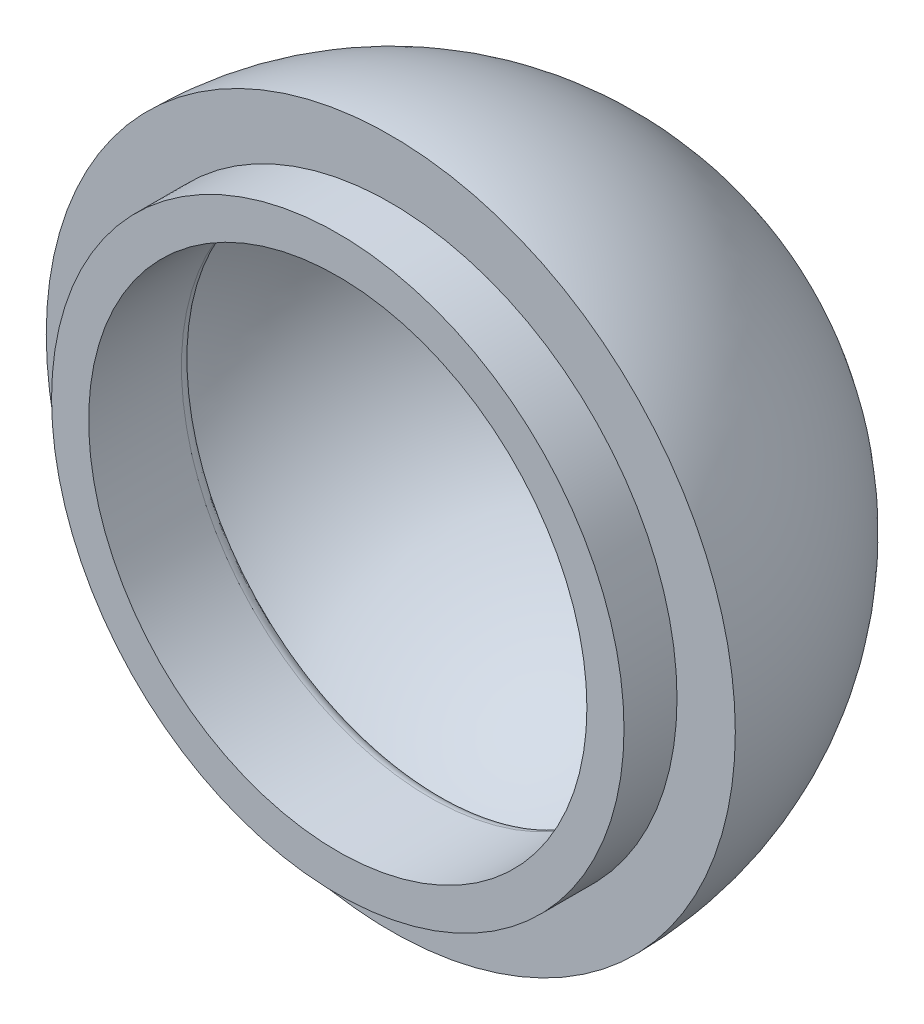
SolidWorks part; units mm, degrees
ref_plane "Front Plane" through (0, 0, 0) normal (0, 0, 1) x (1, 0, 0)
ref_plane "Top Plane" through (0, 0, 0) normal (0, 1, 0) x (1, 0, 0)
ref_plane "Right Plane" through (0, 0, 0) normal (1, 0, 0) x (0, 0, -1)
sketch "Sketch1" plane through (0, 0, 0) normal (0, 0, 1) x (1, 0, 0)
  line L0 (0, 22.4227) -> (0, -31.0825) construction
  line L1 (0, 13) -> (0, 11)
  line L2 (0, -11) -> (0, -13)
  arc A0 (0, 13) -> (0, -13) centre (0, 0) ccw
  arc A1 (0, 11) -> (0, -11) centre (0, 0) ccw
  dimension "D1" = 13
  dimension "D2" = 2
revolve "Revolve1" add sketch "Sketch1" angle 180 about L0
sketch "Sketch2" plane through (0, 0, 0) normal (0, 0, 1) x (1, 0, 0)
  circle A0 centre (0, 0) radius 11
  circle A1 centre (0, 0) radius 10.8
  circle A2 centre (0, 0) radius 11 construction
  dimension "D1" = 0.2
extrude "Boss-Extrude1" add sketch "Sketch2" against normal blind 5
sketch "Sketch3" plane through (0, 0, 0) normal (0, 0, 1) x (1, 0, 0)
  circle A0 centre (0, 0) radius 10.8
  circle A1 centre (0, 0) radius 9.4
  circle A2 centre (0, 0) radius 10.8 construction
  dimension "D1" = 1.4
extrude "Boss-Extrude2" add sketch "Sketch3" along normal mid plane 4
fillet "Fillet2" radius 0.5 1 edges at (9.4, 0, -2)
